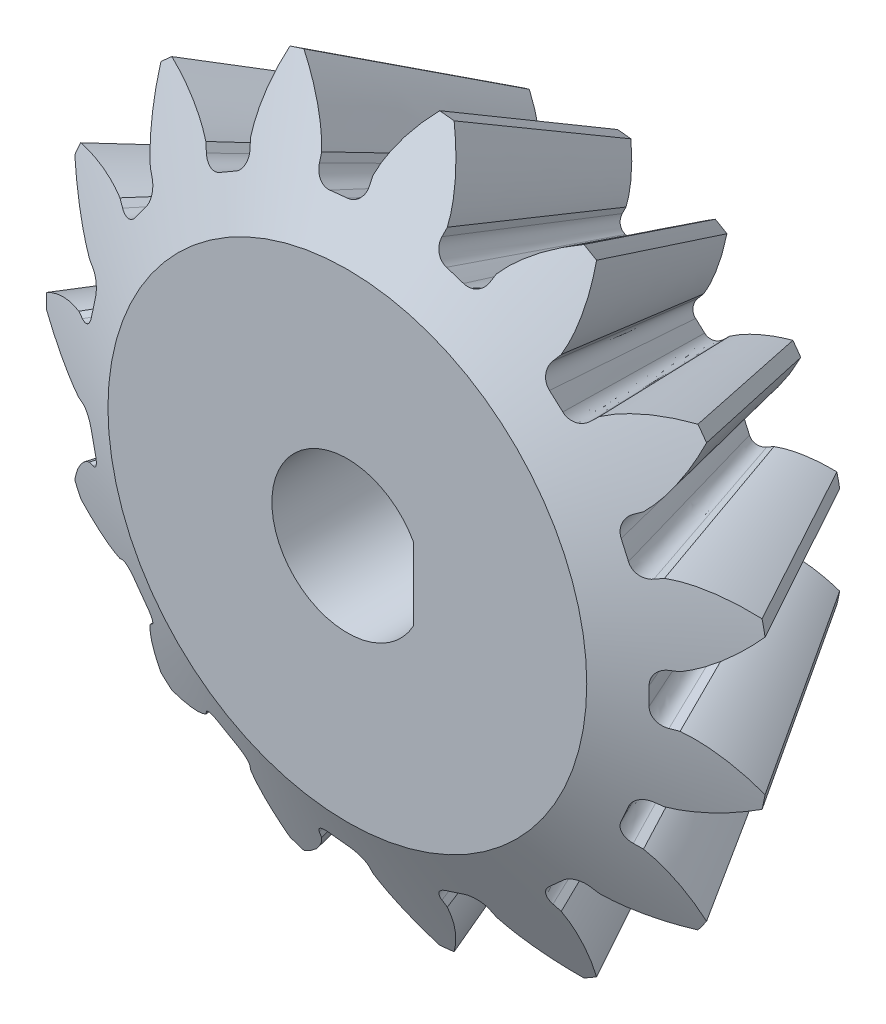
SolidWorks part; units mm, degrees
ref_plane "Front Plane" through (0, 0, 0) normal (0, 0, 1) x (1, 0, 0)
ref_plane "Top Plane" through (0, 0, 0) normal (0, 1, 0) x (1, 0, 0)
ref_plane "Right Plane" through (0, 0, 0) normal (1, 0, 0) x (0, 0, -1)
ref_axis "Gear Axis" through (0, 0, -1.8867) along (0, 0, 1)
sketch "Blank Sketch" plane through (0, 0, 0) normal (0, 1, 0) x (1, 0, 0)
  line L0 (0, 0) -> (0, -37.7336) construction
  line L1 (0, 0) -> (16.875, -33.75) construction
  line L2 (0, 0) -> (11.5084, -23.0169) construction
  line L3 (8.1015, -24.7204) -> (13.2341, -22.1541)
  line L4 (13.2341, -22.1541) -> (19.5818, -32.3966)
  line L5 (19.5818, -32.3966) -> (12.9285, -35.7233)
  line L6 (12.9285, -35.7233) -> (4.075, -35.7233)
  line L7 (4.075, -35.7233) -> (4.075, -24.7204)
  line L8 (4.075, -24.7204) -> (8.1015, -24.7204)
  line L9 (16.875, -33.75) -> (19.5818, -32.3966) construction
  line L10 (16.875, -33.75) -> (12.9285, -35.7233) construction
  line L11 (11.5084, -23.0169) -> (8.1015, -24.7204) construction
  dimension "Axis" = 37.7336
  dimension "Cone" = 26.565
  dimension "Heel" = 37.7336
  dimension "Toe Cone" = 26.565
  dimension "Toe" = 25.7336
  dimension "Heel Square" = 90
  dimension "Addendum" = 3.0263
  dimension "Root Square" = 90
  dimension "Heel Rim" = 4.4123
  dimension "Toe Square" = 90
  dimension "Toe Rim" = 3.8091
  dimension "Front Square" = 90
  dimension "Face" = 5.223
  dimension "Back" = 8.8535
  dimension "Front" = 4.0265
revolve "Blank" add sketch "Blank Sketch" angle 360 about L0
sketch "Cone Sketch" plane through (0, 0, 0) normal (0, 1, 0) x (1, 0, 0)
  line L0 (0, 0) -> (0, -37.7336) construction
  line L1 (0, 0) -> (17.8812, -35.7625)
  line L2 (0, 0) -> (10.5022, -21.0044)
  dimension "Axis" = 37.7336
  dimension "Toe Cone" = 26.565
  dimension "Heel Cone" = 26.565
  dimension "Heel" = 39.9836
  dimension "Toe" = 23.4836
ref_plane "Heel Plane" through (17.8812, 0, 35.7625) normal (0.4472, 0, 0.8944) x (0.8944, 0, -0.4472)
ref_plane "Toe Plane" through (10.5022, 0, 21.0044) normal (0.4472, 0, 0.8944) x (0.8944, 0, -0.4472)
sketch "Heel Section Sketch" plane through (17.8812, 0, 35.7625) normal (0.4472, 0, 0.8944) x (0.8944, 0, -0.4472)
  line L0 (0, 0) -> (-19.9918, 0) construction
  line L1 (-0.7074, 1.4773) -> (-1.1807, 1.4411)
  line L2 (-0.7074, -1.4773) -> (-1.1807, -1.4411)
  line L3 (4.7956, 6.3289) -> (4.7956, -6.3289)
  arc A0 (-1.1807, 1.4411) -> (-2.0171, 0.5119) centre (-1.1115, 0.5377) ccw
  arc A1 (-2.0171, -0.5119) -> (-1.1807, -1.4411) centre (-1.1115, -0.5377) ccw
  arc A2 (-2.0171, -0.5119) -> (-2.0171, 0.5119) centre (-19.9918, 0) ccw
  spline S0 degree 4 poles (-0.9663, 1.4016) (-0.9574, 1.4039) (-0.94, 1.4085) (-0.9108, 1.416) (-0.8439, 1.4347) (-0.7364, 1.4673) (-0.6417, 1.4986) (-0.428, 1.5754) (-0.268, 1.6432) (-0.0438, 1.7417) (0.1524, 1.8399) (0.3635, 1.9503) (0.5606, 2.0629) (0.7611, 2.1832) (0.9544, 2.3069) (1.1472, 2.4364) (1.3695, 2.5935) (1.6352, 2.7927) (1.9373, 3.0343) (2.2765, 3.329) (2.6123, 3.6409) (2.9427, 3.9737) (3.2524, 4.3027) (3.5664, 4.6653) (3.8444, 4.9985) (4.153, 5.404) (4.3826, 5.7121) (4.6987, 6.1784) (4.8531, 6.4156) (5.0563, 6.7411) (5.1378, 6.8792) (5.1883, 6.9642) knots 0 0 0 0 0 0.003968 0.007937 0.015873 0.031746 0.049923 0.07426 0.101525 0.128791 0.156056 0.183322 0.210587 0.237852 0.265118 0.292383 0.319649 0.366669 0.4212 0.475731 0.530261 0.584792 0.639323 0.693854 0.748384 0.802915 0.857446 0.911977 0.955988 1 1 1 1 1 construction
  spline S1 degree 4 poles (-0.7074, 1.4773) (-0.6752, 1.4879) (-0.6021, 1.5129) (-0.428, 1.5754) (-0.268, 1.6432) (-0.0438, 1.7417) (0.1524, 1.8399) (0.3635, 1.9503) (0.5606, 2.0629) (0.7611, 2.1832) (0.9544, 2.3069) (1.1472, 2.4364) (1.3695, 2.5935) (1.6352, 2.7927) (1.9373, 3.0343) (2.2765, 3.329) (2.6123, 3.6409) (2.9427, 3.9737) (3.2524, 4.3027) (3.5664, 4.6653) (3.8444, 4.9985) (4.153, 5.404) (4.3826, 5.7121) (4.6317, 6.0796) (4.7403, 6.2435) (4.7956, 6.3289) knots 0.031746 0.031746 0.031746 0.031746 0.031746 0.049923 0.07426 0.101525 0.128791 0.156056 0.183322 0.210587 0.237852 0.265118 0.292383 0.319649 0.366669 0.4212 0.475731 0.530261 0.584792 0.639323 0.693854 0.748384 0.802915 0.857446 0.911977 0.911977 0.911977 0.911977 0.911977
  spline S2 degree 4 poles (-0.9663, -1.4016) (-0.9574, -1.4039) (-0.94, -1.4085) (-0.9108, -1.416) (-0.8439, -1.4347) (-0.7364, -1.4673) (-0.6417, -1.4986) (-0.428, -1.5754) (-0.268, -1.6432) (-0.0438, -1.7417) (0.1524, -1.8399) (0.3635, -1.9503) (0.5606, -2.0629) (0.7611, -2.1832) (0.9544, -2.3069) (1.1472, -2.4364) (1.3695, -2.5935) (1.6352, -2.7927) (1.9373, -3.0343) (2.2765, -3.329) (2.6123, -3.6409) (2.9427, -3.9737) (3.2524, -4.3027) (3.5664, -4.6653) (3.8444, -4.9985) (4.153, -5.404) (4.3826, -5.7121) (4.6987, -6.1784) (4.8531, -6.4156) (5.0563, -6.7411) (5.1378, -6.8792) (5.1883, -6.9642) knots 0 0 0 0 0 0.003968 0.007937 0.015873 0.031746 0.049923 0.07426 0.101525 0.128791 0.156056 0.183322 0.210587 0.237852 0.265118 0.292383 0.319649 0.366669 0.4212 0.475731 0.530261 0.584792 0.639323 0.693854 0.748384 0.802915 0.857446 0.911977 0.955988 1 1 1 1 1 construction
  spline S3 degree 4 poles (-0.7074, -1.4773) (-0.6752, -1.4879) (-0.6021, -1.5129) (-0.428, -1.5754) (-0.268, -1.6432) (-0.0438, -1.7417) (0.1524, -1.8399) (0.3635, -1.9503) (0.5606, -2.0629) (0.7611, -2.1832) (0.9544, -2.3069) (1.1472, -2.4364) (1.3695, -2.5935) (1.6352, -2.7927) (1.9373, -3.0343) (2.2765, -3.329) (2.6123, -3.6409) (2.9427, -3.9737) (3.2524, -4.3027) (3.5664, -4.6653) (3.8444, -4.9985) (4.153, -5.404) (4.3826, -5.7121) (4.6317, -6.0796) (4.7403, -6.2435) (4.7956, -6.3289) knots 0.031746 0.031746 0.031746 0.031746 0.031746 0.049923 0.07426 0.101525 0.128791 0.156056 0.183322 0.210587 0.237852 0.265118 0.292383 0.319649 0.366669 0.4212 0.475731 0.530261 0.584792 0.639323 0.693854 0.748384 0.802915 0.857446 0.911977 0.911977 0.911977 0.911977 0.911977
  dimension "Root" = 17.982
  dimension "Fillet" = 0.906
  dimension "Centre" = 19.9918
sketch "Toe Section Sketch" plane through (10.5022, 0, 21.0044) normal (0.4472, 0, 0.8944) x (0.8944, 0, -0.4472)
  line L0 (0, 0) -> (-11.7418, 0) construction
  line L1 (-0.4155, 0.8677) -> (-0.6935, 0.8464)
  line L2 (-0.4155, -0.8677) -> (-0.6935, -0.8464)
  line L3 (2.8166, 3.7172) -> (2.8166, -3.7172)
  arc A0 (-0.6935, 0.8464) -> (-1.1847, 0.3007) centre (-0.6528, 0.3158) ccw
  arc A1 (-1.1847, -0.3007) -> (-0.6935, -0.8464) centre (-0.6528, -0.3158) ccw
  arc A2 (-1.1847, -0.3007) -> (-1.1847, 0.3007) centre (-11.7418, 0) ccw
  spline S0 degree 4 poles (-0.5692, 0.8227) (-0.5307, 0.8325) (-0.4537, 0.855) (-0.3971, 0.8728) (-0.2541, 0.9244) (-0.1553, 0.9658) (-0.0271, 1.0225) (0.0904, 1.0809) (0.213, 1.1453) (0.3296, 1.2117) (0.4468, 1.2822) (0.5607, 1.355) (0.6737, 1.431) (0.8044, 1.5232) (0.9604, 1.6402) (1.1379, 1.7822) (1.337, 1.9552) (1.5343, 2.1384) (1.7283, 2.3338) (1.9102, 2.5271) (2.0946, 2.7401) (2.258, 2.9358) (2.4391, 3.1739) (2.5741, 3.3549) (2.7597, 3.6288) (2.8403, 3.7526) (2.9513, 3.9297) (3.0055, 4.0199) (3.033, 4.0661) (3.0468, 4.0896) knots 0 0 0 0 0 0.031746 0.049923 0.07426 0.101525 0.128791 0.156056 0.183322 0.210587 0.237852 0.265118 0.292383 0.319649 0.366669 0.4212 0.475731 0.530261 0.584792 0.639323 0.693854 0.748384 0.802915 0.857446 0.911977 0.955988 0.977994 1 1 1 1 1 construction
  spline S1 degree 4 poles (-0.4155, 0.8677) (-0.3965, 0.8739) (-0.3524, 0.889) (-0.2541, 0.9244) (-0.1553, 0.9658) (-0.0271, 1.0225) (0.0904, 1.0809) (0.213, 1.1453) (0.3296, 1.2117) (0.4468, 1.2822) (0.5607, 1.355) (0.6737, 1.431) (0.8044, 1.5232) (0.9604, 1.6402) (1.1379, 1.7822) (1.337, 1.9552) (1.5343, 2.1384) (1.7283, 2.3338) (1.9102, 2.5271) (2.0946, 2.7401) (2.258, 2.9358) (2.4391, 3.1739) (2.5741, 3.3549) (2.7203, 3.5707) (2.7842, 3.667) (2.8166, 3.7172) knots 0.031746 0.031746 0.031746 0.031746 0.031746 0.049923 0.07426 0.101525 0.128791 0.156056 0.183322 0.210587 0.237852 0.265118 0.292383 0.319649 0.366669 0.4212 0.475731 0.530261 0.584792 0.639323 0.693854 0.748384 0.802915 0.857446 0.911977 0.911977 0.911977 0.911977 0.911977
  spline S2 degree 4 poles (-0.5692, -0.8227) (-0.5307, -0.8325) (-0.4537, -0.855) (-0.3971, -0.8728) (-0.2541, -0.9244) (-0.1553, -0.9658) (-0.0271, -1.0225) (0.0904, -1.0809) (0.213, -1.1453) (0.3296, -1.2117) (0.4468, -1.2822) (0.5607, -1.355) (0.6737, -1.431) (0.8044, -1.5232) (0.9604, -1.6402) (1.1379, -1.7822) (1.337, -1.9552) (1.5343, -2.1384) (1.7283, -2.3338) (1.9102, -2.5271) (2.0946, -2.7401) (2.258, -2.9358) (2.4391, -3.1739) (2.5741, -3.3549) (2.7597, -3.6288) (2.8403, -3.7526) (2.9513, -3.9297) (3.0055, -4.0199) (3.033, -4.0661) (3.0468, -4.0896) knots 0 0 0 0 0 0.031746 0.049923 0.07426 0.101525 0.128791 0.156056 0.183322 0.210587 0.237852 0.265118 0.292383 0.319649 0.366669 0.4212 0.475731 0.530261 0.584792 0.639323 0.693854 0.748384 0.802915 0.857446 0.911977 0.955988 0.977994 1 1 1 1 1 construction
  spline S3 degree 4 poles (-0.4155, -0.8677) (-0.3965, -0.8739) (-0.3524, -0.889) (-0.2541, -0.9244) (-0.1553, -0.9658) (-0.0271, -1.0225) (0.0904, -1.0809) (0.213, -1.1453) (0.3296, -1.2117) (0.4468, -1.2822) (0.5607, -1.355) (0.6737, -1.431) (0.8044, -1.5232) (0.9604, -1.6402) (1.1379, -1.7822) (1.337, -1.9552) (1.5343, -2.1384) (1.7283, -2.3338) (1.9102, -2.5271) (2.0946, -2.7401) (2.258, -2.9358) (2.4391, -3.1739) (2.5741, -3.3549) (2.7203, -3.5707) (2.7842, -3.667) (2.8166, -3.7172) knots 0.031746 0.031746 0.031746 0.031746 0.031746 0.049923 0.07426 0.101525 0.128791 0.156056 0.183322 0.210587 0.237852 0.265118 0.292383 0.319649 0.366669 0.4212 0.475731 0.530261 0.584792 0.639323 0.693854 0.748384 0.802915 0.857446 0.911977 0.911977 0.911977 0.911977 0.911977
  dimension "Root" = 10.5614
  dimension "Fillet" = 0.5321
  dimension "Centre" = 11.7418
loft "Tooth Space" cut profiles "Heel Section Sketch", "Toe Section Sketch"
pattern_circular "Teeth" count 15 over 360 about axis through (0, 0, -1.8867) along (0, 0, 1) of "Tooth Space"
sketch "D-Flat Sketch" plane through (0, 0, 0) normal (0, 0, 1) x (1, 0, 0)
  line L0 (3.575, -2.3894) -> (3.575, 2.3894)
  arc A0 (3.575, -2.3894) -> (3.575, 2.3894) centre (0, 0) ccw
sketch "Sketch2" plane through (0, 0, 0) normal (0, 0, 1) x (1, 0, 0)
  line L0 (3.575, -2.3894) -> (3.575, 2.3894)
  arc A0 (3.575, -2.3894) -> (3.575, 2.3894) centre (0, 0) ccw
extrude "D-Flat" add sketch "Sketch2" along normal blind 11.0029 from offset 24.7204
equation "\"No. of Teeth\"= 15"
equation "\"Module\"= 2.25"
equation "\"Bore Diameter\"= 8.15"
equation "\"Pressure Angle\"= 20"
equation "\"Shaft Angle\"= 90"
equation "\"Mate Teeth\"= 30"
equation "\"Pitch Cone Angle\"= IIF ( ( \"Mate Teeth\" / \"No. of Teeth\" + cos ( \"Shaft Angle\" ) ) > 0 , atn ( sin ( \"Shaft Angle\" ) / ( \"Mate Teeth\" / \"No. of Teeth\" + cos ( \"Shaft Angle\" ) ) ) , 180 + atn ( sin ( \"Shaft Angle\" ) / ( \"Mate Teeth\" / \"No. of Teeth\" + cos ( \"Shaft Angle\" ) ) ) )"
equation "\"Mate Cone Angle\"= \"Shaft Angle\" - \"Pitch Cone Angle\""
equation "\"Addendum\"= IIF ( \"No. of Teeth\" >= \"Mate Teeth\" , 0.54 * \"Module\" + 0.46 * \"Module\" / ( ( \"No. of Teeth\" * cos ( \"Mate Cone Angle\" ) ) / ( \"Mate Teeth\" * cos ( \"Pitch Cone Angle\" ) ) ) , 2 * \"Module\" - ( 0.54 * \"Module\" + 0.46 * \"Module\" / ( ( \"Mate Teeth\" * cos ( \"Pitch Cone Angle\" ) ) / ( \"No. of Teeth\" * cos ( \"Mate Cone Angle\" ) ) ) ) )"
equation "\"Outer Diameter\"= \"No. of Teeth\" * \"Module\" + 2 * \"Addendum\" * cos ( \"Pitch Cone Angle\" )"
equation "\"Pitch Diameter\"= \"No. of Teeth\" * \"Module\""
equation "\"Backlash\"= IIF ( \"Module\" <= 1 , 0.3 * \"Module\" , 0.3 )"
equation "\"Arc Length\"= ( ( \"Module\" * pi ) / 2 + \"Backlash\" - 2 * ( \"Addendum\" - \"Module\" ) * tan ( \"Pressure Angle\" ) )"
equation "\"Fillet Radius\"= 0.38 * \"Module\""
equation "\"Mate Addendum\"= 2 * \"Module\" - \"Addendum\""
equation "\"Dedendum\"= 2.188 * \"Module\" - \"Addendum\""
equation "\"Tooth Depth\"= \"Addendum\" + \"Dedendum\""
equation "\"Mate Dedendum\"= 2.188 * \"Module\" - \"Mate Addendum\""
equation "\"Face Width\"= 12"
equation "\"Cone Distance\"= \"Pitch Diameter\" / ( 2 * sin ( \"Pitch Cone Angle\" ) )"
equation "\"Dedendum Angle\"= atn ( \"Dedendum\" / \"Cone Distance\" )"
equation "\"Mate Dedendum Angle\"= atn ( \"Mate Dedendum\" / \"Cone Distance\" )"
equation "\"Face Angle\"= \"Pitch Cone Angle\" + \"Mate Dedendum Angle\""
equation "\"Root Angle\"= \"Pitch Cone Angle\" - \"Dedendum Angle\""
equation "\"Overrun\"= \"Module\""
equation "\"Back Cone Pitch Diameter\"= \"Pitch Diameter\" / cos ( \"Pitch Cone Angle\" )"
equation "\"Back Cone Outer Diameter\"= \"Back Cone Pitch Diameter\" + 2 * \"Addendum\""
equation "\"Root Diameter\"= \"Back Cone Outer Diameter\" - 2 * \"Tooth Depth\""
equation "\"Base Diameter\"= \"Back Cone Pitch Diameter\" * cos ( \"Pressure Angle\" )"
equation "\"Base Radius\"= \"Base Diameter\" / 2"
equation "\"Tooth Thickness\"= \"Module\" * pi - \"Arc Length\""
equation "\"Half Space Angle\"= ( \"Arc Length\" / \"Back Cone Pitch Diameter\" ) * 180 / pi"
equation "\"Involute Fn\"= tan ( \"Pressure Angle\" ) - \"Pressure Angle\" * pi / 180"
equation "\"Flank Offset\"= \"Arc Length\" / \"Back Cone Pitch Diameter\" - \"Involute Fn\""
equation "\"Tip Cap Diameter\"= \"Back Cone Outer Diameter\" + 2 * \"Module\""
equation "\"Flank Start Diameter\"= IIF ( \"Base Diameter\" >= ( \"Root Diameter\" + 3 * \"Fillet Radius\" ) , \"Base Diameter\" , \"Root Diameter\" + 3 * \"Fillet Radius\" )"
equation "\"Involute t1\"= ( abs ( ( \"Flank Start Diameter\" / \"Base Diameter\" ) ^ 2 - 1 ) ) ^ 0.5"
equation "\"Involute t2\"= ( abs ( ( \"Tip Cap Diameter\" / \"Base Diameter\" ) ^ 2 - 1 ) ) ^ 0.5"
equation "\"Flank Arc Radius\"= ( \"Back Cone Pitch Diameter\" / 2 ) * sin ( \"Pressure Angle\" )"
equation "\"Flank Centre Angle\"= \"Half Space Angle\" + \"Pressure Angle\""
equation "\"Heel Distance\"= \"Cone Distance\" + \"Overrun\""
equation "\"Toe Distance\"= \"Cone Distance\" - \"Face Width\" - \"Overrun\""
equation "\"Heel Scale\"= \"Heel Distance\" / \"Cone Distance\""
equation "\"Toe Scale\"= \"Toe Distance\" / \"Cone Distance\""
equation "\"Heel Virtual Radius\"= \"Heel Distance\" * tan ( \"Pitch Cone Angle\" )"
equation "\"Toe Virtual Radius\"= \"Toe Distance\" * tan ( \"Pitch Cone Angle\" )"
equation "\"Axis@Blank Sketch\"= \"Cone Distance\""
equation "\"Cone@Blank Sketch\"= \"Pitch Cone Angle\""
equation "\"Heel@Blank Sketch\"= \"Cone Distance\""
equation "\"Toe Cone@Blank Sketch\"= \"Pitch Cone Angle\""
equation "\"Toe@Blank Sketch\"= \"Cone Distance\" - \"Face Width\""
equation "\"Addendum@Blank Sketch\"= \"Addendum\""
equation "\"Heel Rim@Blank Sketch\"= \"Dedendum\" + \"Module\" / cos ( \"Pitch Cone Angle\" )"
equation "\"Toe Rim@Blank Sketch\"= \"Dedendum\" - \"Face Width\" * tan ( \"Dedendum Angle\" ) + \"Module\" / cos ( \"Pitch Cone Angle\" )"
equation "\"Face@Blank Sketch\"= \"Mate Dedendum Angle\""
equation "\"Back@Blank Sketch\"= \"Cone Distance\" * sin ( \"Pitch Cone Angle\" ) - \"Dedendum\" * cos ( \"Pitch Cone Angle\" ) - \"Module\" - \"Bore Diameter\" / 2"
equation "\"Front@Blank Sketch\"= ( \"Cone Distance\" - \"Face Width\" ) * sin ( \"Pitch Cone Angle\" ) - ( \"Dedendum\" - \"Face Width\" * tan ( \"Dedendum Angle\" ) + \"Module\" / cos ( \"Pitch Cone Angle\" ) ) * cos ( \"Pitch Cone Angle\" ) - \"Bore Diameter\" / 2"
equation "\"Axis@Cone Sketch\"= \"Cone Distance\""
equation "\"Heel Cone@Cone Sketch\"= \"Pitch Cone Angle\""
equation "\"Heel@Cone Sketch\"= \"Heel Distance\""
equation "\"Toe Cone@Cone Sketch\"= \"Pitch Cone Angle\""
equation "\"Toe@Cone Sketch\"= \"Toe Distance\""
equation "\"Centre@Heel Section Sketch\"= \"Heel Virtual Radius\""
equation "\"Root@Heel Section Sketch\"= ( \"Root Diameter\" / 2 ) * \"Heel Scale\""
equation "\"Fillet@Heel Section Sketch\"= ( \"Fillet Radius\" ) * \"Heel Scale\""
equation "\"Centre@Toe Section Sketch\"= \"Toe Virtual Radius\""
equation "\"Root@Toe Section Sketch\"= ( \"Root Diameter\" / 2 ) * \"Toe Scale\""
equation "\"Fillet@Toe Section Sketch\"= ( \"Fillet Radius\" ) * \"Toe Scale\""
equation "\"Count@Teeth\"= \"No. of Teeth\""
